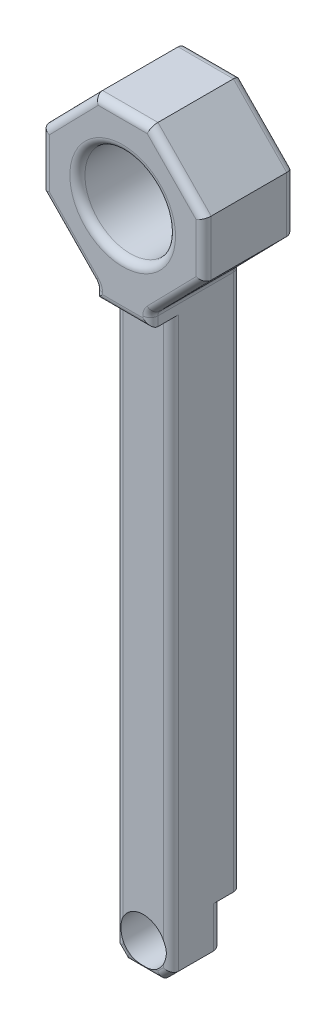
SolidWorks part; units mm, degrees
ref_plane "Front Plane" through (0, 0, 0) normal (0, 0, 1) x (1, 0, 0)
ref_plane "Top Plane" through (0, 0, 0) normal (0, 1, 0) x (1, 0, 0)
ref_plane "Right Plane" through (0, 0, 0) normal (1, 0, 0) x (0, 0, -1)
sketch "Sketch1" plane through (0, 0, 0) normal (0, 0, 1) x (1, 0, 0)
  line L0 (-7.5576, -67.1951) -> (-7.5576, 48.2662)
  line L1 (-7.5576, 48.2662) -> (-18.1436, 59.094)
  line L2 (-18.1436, 59.094) -> (-18.1436, 70.1157)
  line L3 (-18.1436, 70.1157) -> (-7.5576, 80.9435)
  line L4 (-7.5576, 80.9435) -> (3.4424, 80.9435)
  line L5 (3.4424, 80.9435) -> (14.0285, 70.1157)
  line L6 (14.0285, 70.1157) -> (14.0285, 59.094)
  line L7 (14.0285, 59.094) -> (3.4424, 48.2662)
  line L8 (3.4424, 48.2662) -> (3.4424, -67.1951)
  line L9 (1.4424, -69.1951) -> (-5.5576, -69.1951)
  line L10 (-18.1436, 64.6049) -> (14.0285, 64.6049) construction
  line L11 (-5.5576, -69.1951) -> (-7.5576, -67.1951)
  line L12 (3.4424, -67.1951) -> (1.4424, -69.1951)
  circle A0 centre (-2.0576, 64.6049) radius 9
  circle A1 centre (-2.0576, -63.8951) radius 4.5
  point P0 (-7.5576, -69.1951)
  point P10 (3.4424, -69.1951)
  point P21 (-2.0576, -69.1951)
  dimension "D1" = 18
  dimension "D2" = 9
  dimension "D3" = 5.3
  dimension "D4" = 128.5
  dimension "D5" = 11
extrude "Boss-Extrude1" add sketch "Sketch1" along normal blind 18
sketch "Sketch2" plane through (-7.5576, 0, 0) normal (-1, 0, 0) x (0, 0, 1)
  line L0 (3.9206, -84.3985) -> (3.9206, -59.021)
  line L1 (3.9206, -59.021) -> (-18.5826, -59.021)
  line L2 (-18.5826, -59.021) -> (-18.5826, -119.5048)
  line L3 (-18.5826, -119.5048) -> (35.5811, -119.5048)
  line L4 (35.5811, -119.5048) -> (35.5811, 45.8028)
  line L5 (35.5811, 45.8028) -> (13.9206, 45.8028)
  line L6 (13.9206, 45.8028) -> (13.9206, -84.3985)
  line L7 (13.9206, -84.3985) -> (3.9206, -84.3985)
  dimension "D1" = 10
extrude "Cut-Extrude1" cut sketch "Sketch2" against normal through all both and the other way through all
fillet "Fillet1" radius 1.5 32 edges at (6.9424, 64.6049, 18) (-7.5576, 47.0345, 18) (-12.8506, 53.6801, 18) (-18.1436, 64.6049, 18) (-12.8506, 75.5296, 18) (-2.0576, 80.9435, 18) (8.7355, 75.5296, 18) (14.0285, 64.6049, 18) (8.7355, 53.6801, 18) (3.4424, 47.0345, 18) (-2.0576, 45.8028, 18) (-7.5576, -10.6962, 13.9206) (-6.5576, -68.1951, 13.9206) (-2.0576, -69.1951, 13.9206) (2.4424, -68.1951, 13.9206) (3.4424, -10.6962, 13.9206) (3.4424, -63.1081, 3.9206) (2.4424, -68.1951, 3.9206) (-2.0576, -69.1951, 3.9206) (-7.5576, -63.1081, 3.9206) (-6.5576, -68.1951, 3.9206) (3.4424, 48.2662, 9) (-7.5576, 48.2662, 9) (-7.5576, -5.3774, 0) (-12.8506, 53.6801, 0) (-18.1436, 64.6049, 0) (-12.8506, 75.5296, 0) (-2.0576, 80.9435, 0) (8.7355, 75.5296, 0) (14.0285, 64.6049, 0) (8.7355, 53.6801, 0) (3.4424, -5.3774, 0)
sketch "Sketch3" plane through (0, 0, 0) normal (0, 0, -1) x (-1, 0, 0)
  line L1 (-0.8235, -15.9954) -> (4.7792, -15.9954)
  line L2 (-0.8235, -15.9954) -> (-0.8235, -54.6399)
  line L3 (-0.8235, -54.6399) -> (4.7792, -54.6399)
  line L4 (4.7792, -15.9954) -> (4.7792, -54.6399)
  line L5 (-0.8235, 23.2238) -> (4.7792, 23.2238)
  line L6 (-0.8235, 23.2238) -> (-0.8235, -7.8068)
  line L7 (-0.8235, -7.8068) -> (4.7792, -7.8068)
  line L8 (4.7792, 23.2238) -> (4.7792, -7.8068)
  line L9 (-0.8235, 50.8065) -> (4.7792, 50.8065)
  line L10 (-0.8235, 50.8065) -> (-0.8235, 29.4012)
  line L11 (-0.8235, 29.4012) -> (4.7792, 29.4012)
  line L12 (4.7792, 50.8065) -> (4.7792, 29.4012)
extrude "Cut-Extrude2" [suppressed] cut sketch "Sketch3" against normal through all both and the other way through all
